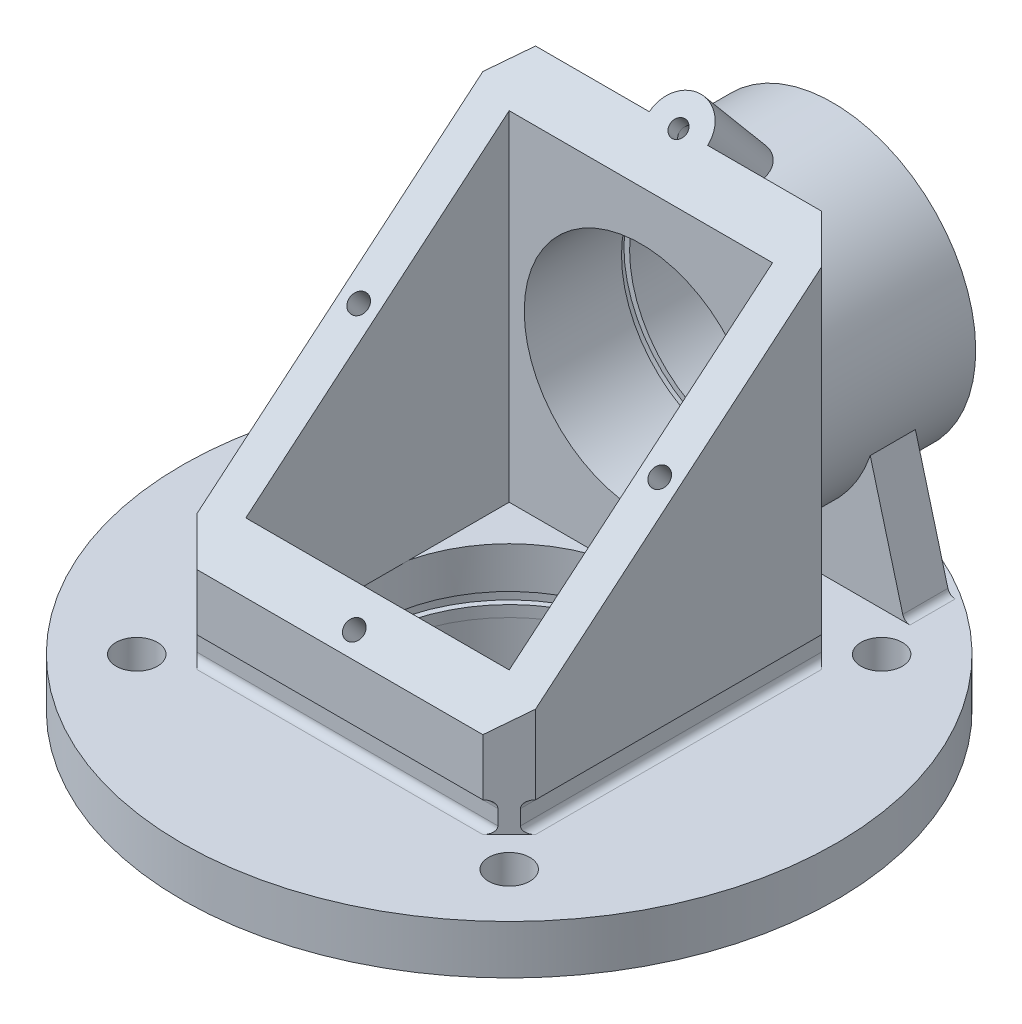
SolidWorks part; units mm, degrees
ref_plane "Front Plane" through (0, 0, 0) normal (1, 0, 0) x (0, 1, 0)
ref_plane "Top Plane" through (0, 0, 0) normal (0, 0, 1) x (0, 1, 0)
ref_plane "Right Plane" through (0, 0, 0) normal (0, 1, 0) x (-1, 0, 0)
sketch "Sketch1" plane through (0, 0, 0) normal (0, 1, 0) x (-1, 0, 0)
  line L1 (-35, 35) -> (35, 35)
  line L2 (-35, 35) -> (-35, -35)
  line L3 (-35, -35) -> (35, -35)
  line L4 (35, 35) -> (35, -35)
  line L5 (-35, 35) -> (35, -35) construction
  line L6 (-35, -35) -> (35, 35) construction
  line L7 (-45, 45) -> (45, 45)
  line L8 (-45, 45) -> (-45, -45)
  line L9 (-45, -45) -> (45, -45)
  line L10 (45, 45) -> (45, -45)
  line L11 (-45, 45) -> (45, -45) construction
  line L12 (-45, -45) -> (45, 45) construction
  point P0 (0, 0)
  point P6 (0, 0)
  dimension "D1" = 90
  dimension "D2" = 70
  dimension "D3" = 90
  dimension "D4" = 70
extrude "Boss-Extrude1" add sketch "Sketch1" against normal blind 23 and the other way blind 80 contours L10 L7 L8 L9 L1 L4 L3 L2 region at (0, 0, 43.7272)
sketch "Sketch2" plane through (0, 0, 0) normal (1, 0, 0) x (0, 1, 0)
  line L0 (0, 45) -> (80, -50.3403)
  line L1 (80, 45) -> (-23, 45) construction
  line L2 (0, 0) -> (0, 49.6736) construction
  line L3 (0, 45) -> (80, 45)
  line L4 (80, 45) -> (80, -50.3403)
  dimension "D1" = 40
extrude "Cut-Extrude1" cut sketch "Sketch2" against normal through all both and the other way through all
sketch "Sketch3" plane through (0, -23, 0) normal (0, -1, 0) x (1, 0, 0)
  circle A0 centre (0, 0) radius 87
  dimension "D1" = 174
extrude "Boss-Extrude2" add sketch "Sketch3" along normal blind 13
ref_plane "Plane2" through (0, 0, -86) normal (0, 0, 1) x (0, 1, 0)
sketch "Sketch4" plane through (0, 0, -86) normal (0, 0, 1) x (0, 1, 0)
  line L0 (0, 0) -> (-23, 0) construction
  line L1 (0, 0) -> (0, 50000) construction
  line L2 (-23, 15) -> (-11.9142, 15)
  line L3 (-23, -45) -> (-23, 45) construction
  line L4 (-23, -15) -> (-11.9142, -15)
  line L5 (-23, 15) -> (-23, -15)
  arc A0 (-11.9142, -15) -> (-11.9142, 15) centre (23, 0) ccw
  circle A1 centre (23, 0) radius 31
  dimension "D1" = 76
  dimension "D4" = 62
  dimension "D2" = 23
  dimension "D3" = 46
  dimension "D5" = 30
extrude "Boss-Extrude3" add sketch "Sketch4" along normal up to surface (41 mm away) up to face at (0, 26.2595, -45)
ref_plane "Plane3" through (0, 0, -72) normal (0, 0, 1) x (0, 1, 0)
sketch "Sketch5" plane through (0, 0, -72) normal (0, 0, 1) x (0, 1, 0)
  line L0 (-23, -15) -> (-11.9142, -15) construction
  line L1 (-23, -15) -> (-11.9142, -15)
  line L2 (-11.9142, 15) -> (-23, 15)
  line L3 (-23, -45) -> (-23, 45) construction
  line L4 (0, 0) -> (39.8176, 0) construction
  line L5 (10.726, -35.9632) -> (-23, -45)
  line L6 (10.726, 35.9632) -> (-23, 45)
  line L7 (-23, 45) -> (-23, 15)
  line L8 (-23, -15) -> (-23, -45)
  arc A0 (-11.9142, -15) -> (-11.9142, 15) centre (23, 0) ccw construction
  arc A1 (-11.9142, -15) -> (10.726, -35.9632) centre (23, 0) ccw
  arc A3 (10.726, 35.9632) -> (-11.9142, 15) centre (23, 0) ccw
  dimension "D1" = 15
  dimension "D2" = 45
extrude "Boss-Extrude4" add sketch "Sketch5" along normal blind 12
fillet "Fillet1" radius 2 2 edges at (-45, -23, -66) (45, -23, -66)
fillet "Fillet2" radius 2 4 edges at (-15, -23, -78.8486) (-15, -23, -52.5) (15, -23, -78.8486) (15, -23, -52.5)
sketch "Sketch7" plane through (0, 22.1582, 18.5929) normal (0, 0.766, 0.6428) x (-1, 0, 0)
  line L0 (45, -83.0147) -> (-45, -83.0147) construction
  line L1 (-7.74, -83.0147) -> (-7.74, -69.9606)
  line L2 (35, -69.9606) -> (-35, -69.9606) construction
  line L3 (-7.74, -69.9606) -> (7.74, -69.9606)
  line L4 (7.74, -69.9606) -> (7.74, -83.0147)
  arc A0 (-7.74, -83.0147) -> (7.74, -83.0147) centre (0, -83.0147) ccw
  dimension "D1" = 15.48
extrude "Boss-Extrude5" add sketch "Sketch7" against normal up to surface (9.0394 mm away) up to face at (0, 7.0438, -65.8333)
sketch "Sketch8" plane through (0, 22.1582, 18.5929) normal (0, 0.766, 0.6428) x (-1, 0, 0)
  circle A0 centre (0, -83.0147) radius 2.2284
extrude "Cut-Extrude2" cut sketch "Sketch8" against normal blind 4
hole_wizard "M6 Tapped Hole1" positions "3DSketch2" profile "Sketch10" tap size "M6" standard "ISO"
sketch3d "3DSketch2"
  line L0 (0, 72.4548, -47.5712) -> (0, 75.519, -45) construction
  line L1 (0, 61.3269, -56.9086) -> (0, 77.278, -43.524) construction
  point P0 (0, 72.4548, -47.5712)
  point P4 (0, 75.519, -45)
sketch "Sketch10" plane through (0, 72.4548, -47.5712) normal (1, 0, 0) x (0, -0.6428, 0.766)
  line L0 (0, 0) -> (0, 17.5022)
  line L1 (0, 17.5022) -> (2.5, 16)
  line L2 (2.5, 16) -> (2.5, 0)
  line L5 (2.5, 0) -> (0, 0)
  line L10 (0, 17.5022) -> (-2.5, 16) construction
  line L11 (0, -6.35) -> (0, 107.95) construction
  dimension "Tap Drill Dia." = 5
  dimension "Tap Drill Depth" = 16
  dimension "Drill Angle" = 118
chamfer "Chamfer1" distance 7 angle 45 4 edges at (-45, 26.2595, -45) (45, 26.2595, -45) (-45, -11.5, 45) (45, -11.5, 45)
sketch "Sketch11" plane through (0, -36, 0) normal (0, -1, 0) x (1, 0, 0)
  circle A0 centre (0, 0) radius 46
  dimension "D1" = 92
extrude "Boss-Extrude6" add sketch "Sketch11" along normal blind 4
sketch "Sketch12" plane through (0, 0, 0) normal (1, 0, 0) x (0, 1, 0)
  line L0 (-40, 46) -> (-81.9448, 46) construction
  line L1 (-40, 46) -> (-55, 40.5404)
  line L2 (-36, 87) -> (-36, -87) construction
  line L4 (-40, 46) -> (-40, -46) construction
  line L6 (-55, 40.5404) -> (-55, 36.1479)
  line L7 (-55, 36.1479) -> (-40, 36.1479)
  line L8 (0, 0) -> (-87.4142, 0) construction
  line L9 (-40, 46) -> (-40, 36.1479)
  point P11 (-40, 0.1479)
  dimension "D1" = 19
  dimension "D2" = 20
  dimension "D4" = 9.8521
revolve "Revolve1" add sketch "Sketch12" angle 360 about L8
chamfer "Chamfer2" distance 1 angle 45 1 edges at (0, -55, 36.1479)
sketch "Sketch13" plane through (45, 0, 0) normal (1, 0, 0) x (0, 1, 0)
  line L0 (-23, 45) -> (-15, 45)
  line L1 (-23, 45) -> (0, 45) construction
  line L2 (-21, 43) -> (-17, 43)
  arc A0 (-17, 43) -> (-15, 45) centre (-17, 45) ccw
  arc A1 (-23, 45) -> (-21, 43) centre (-21, 45) ccw
  dimension "D2" = 4
  dimension "D3" = 4
  dimension "D1" = 8
extrude "Cut-Extrude3" cut sketch "Sketch13" against normal through all both and the other way through all
sketch "Sketch14" plane through (15, 0, 0) normal (1, 0, 0) x (0, 1, 0)
  line L0 (-23, -86) -> (-11.9142, -86) construction
  line L1 (-21, -84) -> (-17, -84)
  line L2 (-23, -86) -> (-15, -86)
  arc A0 (-15, -86) -> (-17, -84) centre (-17, -86) ccw
  arc A1 (-21, -84) -> (-23, -86) centre (-21, -86) ccw
  point P6 (-15, -86)
  point P8 (-23, -86)
  dimension "D1" = 4
  dimension "D2" = 4
  dimension "D3" = 8
extrude "Cut-Extrude4" cut sketch "Sketch14" against normal through all both and the other way through all
sketch "Sketch15" plane through (0, 0, 45) normal (0, 0, 1) x (1, 0, 0)
  line L0 (-45, -23) -> (-45, 5.8737) construction
  line L1 (-43, -17) -> (-43, -21)
  line L2 (-45, -15) -> (-45, -23)
  arc A0 (-43, -17) -> (-45, -15) centre (-45, -17) ccw
  arc A1 (-45, -23) -> (-43, -21) centre (-45, -21) ccw
  dimension "D1" = 4
  dimension "D2" = 4
extrude "Cut-Extrude6" cut sketch "Sketch15" against normal blind 100 and the other way through all contours L2 A1 L1 A0
mirror "Mirror1" about plane through (0, 0, 0) normal (1, 0, 0) of "Cut-Extrude6"
sketch "Sketch16" plane through (0, -40, 0) normal (0, -1, 0) x (1, 0, 0)
  circle A0 centre (0, 0) radius 36
  dimension "D1" = 72
extrude "Cut-Extrude7" cut sketch "Sketch16" against normal up to surface (17 mm away) up to face at (0, -23, 0)
sketch "Sketch17" plane through (0, 0, -45) normal (0, 0, -1) x (1, 0, 0)
  circle A0 centre (0, -23) radius 32.5
ref_plane "Plane4" through (0, -15, 0) normal (0, 1, 0) x (1, 0, 0)
ref_plane "Plane5" through (0, -34, 0) normal (0, 1, 0) x (1, 0, 0)
sketch "Sketch18" plane through (0, 0, 0) normal (1, 0, 0) x (0, 1, 0)
  line L0 (-37, 37.5) -> (-34, 37.5)
  line L1 (-34, 37.5) -> (-34, 0)
  line L2 (74.5218, 0) -> (-74.5218, 0) construction
  line L3 (-37, 37.5) -> (-37, 0)
  line L4 (0, 0) -> (-59.3083, 0) construction
  line L5 (-15, -94.7776) -> (-15, 94.7776) construction
  line L6 (-37, 0) -> (-34, 0)
  dimension "D1" = 19
  dimension "D2" = 3
  dimension "D3" = 75
revolve "Cut-Revolve3" cut sketch "Sketch18" angle 360 about L4
ref_plane "Plane6" through (0, 0, -81) normal (0, 0, -1) x (-1, 0, 0)
sketch "Sketch19" plane through (0, 0, -81) normal (0, 0, -1) x (-1, 0, 0)
  circle A0 centre (0, 23) radius 32.5
  dimension "D1" = 65
extrude "Cut-Extrude9" cut sketch "Sketch19" against normal blind 2.15 contours A0
ref_plane "Plane7" through (0, 0, -63) normal (0, 0, -1) x (-1, 0, 0)
sketch "Sketch20" plane through (0, 0, -63) normal (0, 0, -1) x (-1, 0, 0)
  circle A0 centre (0, 23) radius 32.5
  dimension "D1" = 65
extrude "Cut-Extrude10" cut sketch "Sketch20" against normal blind 2.15
sketch "Sketch21" plane through (0, 0, -45) normal (0, 0, -1) x (1, 0, 0)
  circle A0 centre (0, -23) radius 31
  dimension "D1" = 62
extrude "Cut-Extrude11" cut sketch "Sketch21" against normal up to surface (10 mm away) up to face at (0, 7.0427, -35)
sketch "Sketch22" plane through (0, -23, 0) normal (0, 1, 0) x (-1, 0, 0)
  line L0 (0, 0) -> (-49.4975, 49.4975) construction
  line L1 (0, 0) -> (-53.0273, 0) construction
  circle A0 centre (0, 0) radius 70 construction
  circle A1 centre (-49.4975, 49.4975) radius 5.5
  dimension "D1" = 140
  dimension "D2" = 11
  dimension "D3" = 45
extrude "Cut-Extrude12" cut sketch "Sketch22" against normal through all
pattern_circular "CirPattern1" count 4 over 360 about axis through (0, -23, 0) along (0, -1, 0) of "Cut-Extrude12"
sketch "Sketch23" plane through (0, 22.1582, 18.5929) normal (0, 0.766, 0.6428) x (-1, 0, 0)
  line L0 (0, 34.472) -> (0, 29.472) construction
  line L1 (38, 34.472) -> (-38, 34.472) construction
  line L2 (0, 29.472) -> (0, -24.268) construction
  line L3 (-45, -24.2713) -> (-40, -24.2713) construction
  line L4 (-45, 25.3341) -> (-45, -73.8768) construction
  line L5 (45, -24.2713) -> (40, -24.2713) construction
  point P13 (0, 29.472)
  point P14 (-40, -24.2713)
  point P15 (40, -24.2713)
  dimension "D1" = 5
  dimension "D2" = 53.74
  dimension "D3" = 5
hole_wizard "Tap Drill for M6 Tap1" positions "Sketch23" profile "Sketch24" hole size "M6" standard "ISO"
sketch "Sketch24" plane through (-40, 37.7595, 0) normal (1, 0, 0) x (0, -0.6428, 0.766)
  line L0 (0, 0) -> (0, 14.5022)
  line L1 (0, 14.5022) -> (2.5, 13)
  line L2 (2.5, 13) -> (2.5, 0)
  line L5 (2.5, 0) -> (0, 0)
  line L10 (0, 14.5022) -> (-2.5, 13) construction
  line L11 (0, -6.35) -> (0, 107.95) construction
  dimension "Hole Dia." = 5
  dimension "Hole Depth" = 13
  dimension "Drill Angle" = 118
